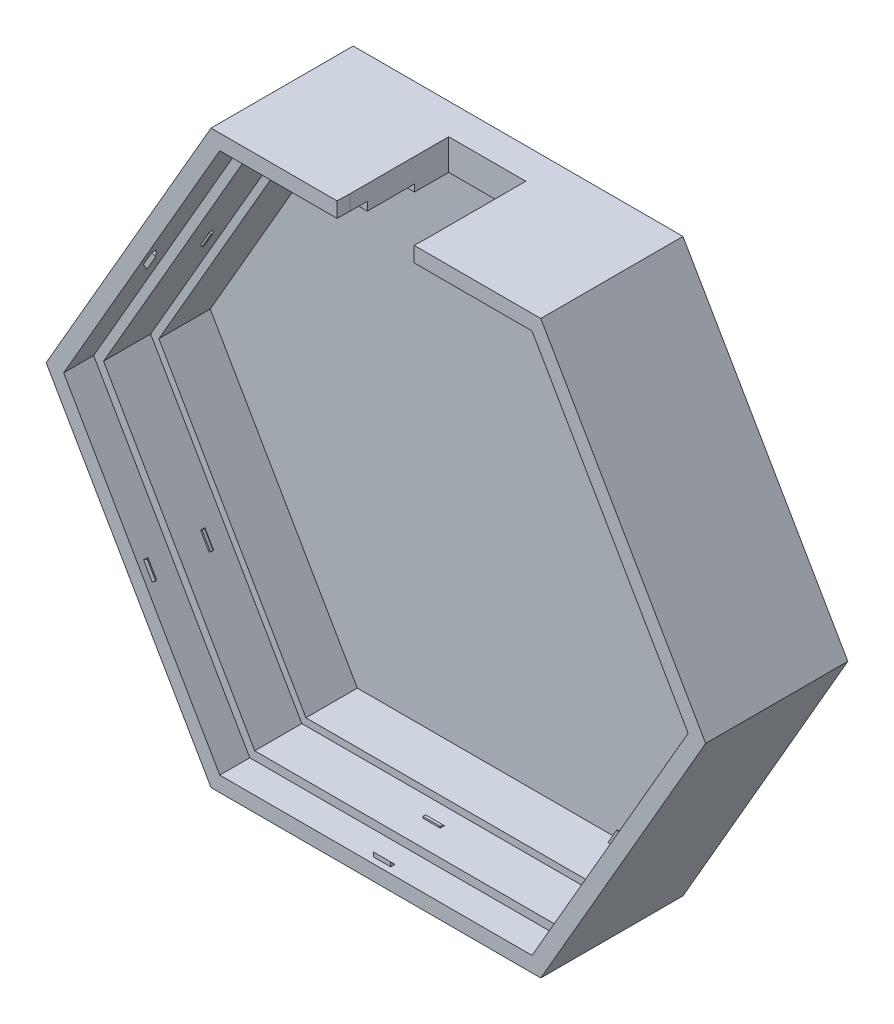
SolidWorks part; units mm, degrees
ref_plane "Front Plane" through (0, 0, 0) normal (0, 0, 1) x (1, 0, 0)
ref_plane "Top Plane" through (0, 0, 0) normal (0, 1, 0) x (1, 0, 0)
ref_plane "Right Plane" through (0, 0, 0) normal (1, 0, 0) x (0, 0, -1)
sketch "Sketch1" plane through (0, 0, 0) normal (0, 0, 1) x (1, 0, 0)
  line L1 (35.5, 0) -> (17.75, 30.7439)
  line L2 (17.75, 30.7439) -> (-17.75, 30.7439)
  line L3 (-17.75, 30.7439) -> (-35.5, 0)
  line L4 (-35.5, 0) -> (-17.75, -30.7439)
  line L5 (-17.75, -30.7439) -> (17.75, -30.7439)
  line L6 (17.75, -30.7439) -> (35.5, 0)
  line L7 (37.3475, 0) -> (18.6738, 32.3439)
  line L8 (18.6738, 32.3439) -> (-18.6738, 32.3439)
  line L9 (-18.6738, 32.3439) -> (-37.3475, 0)
  line L10 (-37.3475, 0) -> (-18.6738, -32.3439)
  line L11 (-18.6738, -32.3439) -> (18.6738, -32.3439)
  line L12 (18.6738, -32.3439) -> (37.3475, 0)
  circle A0 centre (0, 0) radius 30.7439 construction
  circle A1 centre (0, 0) radius 32.3439 construction
  dimension "D1" = 35.5
  dimension "D2" = 1.6
extrude "Boss-Extrude1" add sketch "Sketch1" along normal blind 10
sketch "Sketch2" plane through (0, 0, 0) normal (0, 0, -1) x (-1, 0, 0)
  line L1 (36.8475, 0) -> (18.4238, 31.9109)
  line L2 (18.4238, 31.9109) -> (-18.4238, 31.9109)
  line L3 (-18.4238, 31.9109) -> (-36.8475, 0)
  line L4 (-36.8475, 0) -> (-18.4238, -31.9109)
  line L5 (-18.4238, -31.9109) -> (18.4238, -31.9109)
  line L6 (18.4238, -31.9109) -> (36.8475, 0)
  circle A0 centre (0, 0) radius 31.9109 construction
extrude "Boss-Extrude2" add sketch "Sketch2" along normal blind 1.6
sketch "Sketch8" plane through (0, 0, 0) normal (0, 0, -1) x (-1, 0, 0)
  line L1 (18.6738, -32.3439) -> (37.3475, 0)
  line L2 (37.3475, 0) -> (18.6738, 32.3439)
  line L3 (18.6738, 32.3439) -> (-18.6738, 32.3439)
  line L4 (-18.6738, 32.3439) -> (-37.3475, 0)
  line L5 (-37.3475, 0) -> (-18.6738, -32.3439)
  line L6 (-18.6738, -32.3439) -> (18.6738, -32.3439)
  circle A0 centre (0, 0) radius 32.3439 construction
extrude "Boss-Extrude5" add sketch "Sketch8" along normal blind 1.6
sketch "Sketch9" plane through (0, 0, 0) normal (0, 0, 1) x (1, 0, 0)
  line L0 (-17.75, 30.7439) -> (-35.5, 0) construction
  line L1 (-34.3453, 0) -> (-17.1726, -29.7439)
  line L2 (-17.1726, -29.7439) -> (17.1726, -29.7439)
  line L3 (17.1726, -29.7439) -> (34.3453, 0)
  line L4 (34.3453, 0) -> (17.1726, 29.7439)
  line L5 (17.1726, 29.7439) -> (-17.1726, 29.7439)
  line L6 (-17.1726, 29.7439) -> (-34.3453, 0)
  line L8 (-17.75, 30.7439) -> (-35.5, 0)
  line L9 (-35.5, 0) -> (-17.75, -30.7439)
  line L10 (-17.75, -30.7439) -> (17.75, -30.7439)
  line L11 (17.75, -30.7439) -> (35.5, 0)
  line L12 (35.5, 0) -> (17.75, 30.7439)
  line L13 (17.75, 30.7439) -> (-17.75, 30.7439)
  circle A0 centre (0, 0) radius 29.7439 construction
  circle A1 centre (0, 0) radius 30.7439 construction
  dimension "D1" = 1
extrude "Boss-Extrude6" add sketch "Sketch9" along normal blind 2
sketch "Sketch10" plane through (0, 30.7439, 0) normal (0, -1, 0) x (1, 0, 0)
  line L0 (17.75, 2) -> (-17.75, 2) construction
  line L1 (-4.5, 2) -> (4.5, 2)
  line L2 (-4.5, 2) -> (-4.5, 10)
  line L3 (-4.5, 10) -> (4.5, 10)
  line L4 (4.5, 2) -> (4.5, 10)
  line L5 (17.75, 10) -> (-17.75, 10) construction
  line L6 (-17.75, 10) -> (-17.75, 2) construction
  dimension "D1" = 9
  dimension "D2" = 13.25
extrude "Cut-Extrude1" cut sketch "Sketch10" against normal blind 2
sketch "Sketch11" plane through (0, 0, 2) normal (0, 0, 1) x (1, 0, 0)
  line L1 (35.3, 0) -> (17.65, 30.5707)
  line L2 (17.65, 30.5707) -> (-17.65, 30.5707)
  line L3 (-17.65, 30.5707) -> (-35.3, 0)
  line L4 (-35.3, 0) -> (-17.65, -30.5707)
  line L5 (-17.65, -30.5707) -> (17.65, -30.5707)
  line L6 (17.65, -30.5707) -> (35.3, 0)
  line L7 (35.5, 0) -> (17.75, 30.7439)
  line L8 (17.75, 30.7439) -> (-17.75, 30.7439)
  line L9 (-17.75, 30.7439) -> (-35.5, 0)
  line L10 (-35.5, 0) -> (-17.75, -30.7439)
  line L11 (-17.75, -30.7439) -> (17.75, -30.7439)
  line L12 (17.75, -30.7439) -> (35.5, 0)
  circle A0 centre (0, 0) radius 30.5707 construction
  circle A1 centre (0, 0) radius 30.7439 construction
  dimension "D1" = 35.3
extrude "Boss-Extrude7" add sketch "Sketch11" along normal blind 8
sketch "Sketch12" plane through (0, 0, 10) normal (0, 0, 1) x (1, 0, 0)
  line L1 (37.3475, 0) -> (18.6738, 32.3439)
  line L2 (18.6738, 32.3439) -> (-18.6738, 32.3439)
  line L3 (-18.6738, 32.3439) -> (-37.3475, 0)
  line L4 (-37.3475, 0) -> (-18.6738, -32.3439)
  line L5 (-18.6738, -32.3439) -> (18.6738, -32.3439)
  line L6 (18.6738, -32.3439) -> (37.3475, 0)
  circle A0 centre (0, 0) radius 32.3439 construction
extrude "Cut-Extrude2" cut sketch "Sketch12" against normal blind 4
sketch "Sketch13" plane through (0, 30.7439, 0) normal (0, 1, 0) x (1, 0, 0)
  line L1 (4.5, -2) -> (-4.5, -2)
  line L2 (4.5, -2) -> (4.5, -6)
  line L3 (4.5, -6) -> (-4.5, -6)
  line L4 (-4.5, -2) -> (-4.5, -6)
extrude "Cut-Extrude3" cut sketch "Sketch13" against normal blind 4
sketch "Sketch16" plane through (0, 32.3439, 0) normal (0, 1, 0) x (1, 0, 0)
  line L0 (4.5, -2) -> (-4.5, -2)
  line L1 (-4.5, -2) -> (-4.5, 0)
  line L2 (-4.5, 0) -> (4.5, 0)
  line L3 (4.5, 0) -> (4.5, -2)
  dimension "D1" = 2
extrude "Cut-Extrude4" cut sketch "Sketch16" against normal blind 3
sketch "Sketch19" plane through (0, 0, -1.6) normal (0, 0, -1) x (-1, 0, 0)
  line L0 (-19.2511, 33.3439) -> (-38.5022, 0)
  line L1 (-18.6738, 32.3439) -> (-37.3475, 0)
  line L2 (-37.3475, 0) -> (-18.6738, -32.3439)
  line L3 (-18.6738, -32.3439) -> (18.6738, -32.3439)
  line L4 (18.6738, -32.3439) -> (37.3475, 0)
  line L5 (37.3475, 0) -> (18.6738, 32.3439)
  line L6 (18.6738, 32.3439) -> (-18.6738, 32.3439)
  line L7 (-38.5022, 0) -> (-19.2511, -33.3439)
  line L8 (-19.2511, -33.3439) -> (19.2511, -33.3439)
  line L9 (19.2511, -33.3439) -> (38.5022, 0)
  line L10 (38.5022, 0) -> (19.2511, 33.3439)
  line L11 (19.2511, 33.3439) -> (-19.2511, 33.3439)
  line L12 (-18.0964, -31.3439) -> (18.0964, -31.3439)
  line L13 (18.0964, -31.3439) -> (36.1928, 0)
  line L14 (36.1928, 0) -> (18.0964, 31.3439)
  line L15 (18.0964, 31.3439) -> (-18.0964, 31.3439)
  line L16 (-18.0964, 31.3439) -> (-36.1928, 0)
  line L17 (-36.1928, 0) -> (-18.0964, -31.3439)
  circle A0 centre (0, 0) radius 32.3439 construction
  line M13 (-18.6738, -32.3439) -> (18.6738, -32.3439)
  line M14 (18.6738, -32.3439) -> (37.3475, 0)
  line M15 (37.3475, 0) -> (18.6738, 32.3439)
  line M16 (18.6738, 32.3439) -> (-18.6738, 32.3439)
  line M17 (-18.6738, 32.3439) -> (-37.3475, 0)
  line M18 (-37.3475, 0) -> (-18.6738, -32.3439)
  dimension "D1" = 1
  dimension "D2" = 1
extrude "Boss-Extrude10" add sketch "Sketch19" against normal blind 7.6 contours L10 L11 L0 L7 L8 L9 M13 M18 M17 M16 M15 M14 region at (0, 33.242, -1.6)
sketch "Sketch21" plane through (0, 0, 6) normal (0, 0, 1) x (1, 0, 0)
  line L0 (4.5, 32.3439) -> (4.5, 33.3439)
  line L1 (-19.2511, 33.3439) -> (19.2511, 33.3439) construction
  line L2 (4.5, 33.3439) -> (-4.5, 33.3439)
  line L3 (-4.5, 33.3439) -> (-4.5, 32.3439)
  line L4 (-4.5, 32.3439) -> (4.5, 32.3439)
extrude "Cut-Extrude5" cut sketch "Sketch21" against normal blind 6
sketch "Sketch22" plane through (0, 0, 6) normal (0, 0, 1) x (1, 0, 0)
  line L0 (-35.3, 0) -> (-17.65, -30.5707) construction
  line L1 (-36.4547, 0) -> (-18.2274, -31.5707)
  line L2 (-18.2274, -31.5707) -> (18.2274, -31.5707)
  line L3 (18.2274, -31.5707) -> (36.4547, 0)
  line L4 (36.4547, 0) -> (18.2274, 31.5707)
  line L5 (18.2274, 31.5707) -> (-18.2274, 31.5707)
  line L6 (-18.2274, 31.5707) -> (-36.4547, 0)
  circle A0 centre (0, 0) radius 31.5707 construction
  dimension "D1" = 1
extrude "Cut-Extrude7" cut sketch "Sketch22" against normal blind 2.2
sketch "Sketch24" plane through (0, 0, -1.6) normal (0, 0, -1) x (-1, 0, 0)
  line L1 (-19.2511, -33.3439) -> (19.2511, -33.3439)
  line L2 (19.2511, -33.3439) -> (38.5022, 0)
  line L3 (38.5022, 0) -> (19.2511, 33.3439)
  line L4 (19.2511, 33.3439) -> (-19.2511, 33.3439)
  line L5 (-19.2511, 33.3439) -> (-38.5022, 0)
  line L6 (-38.5022, 0) -> (-19.2511, -33.3439)
  circle A0 centre (0, 0) radius 33.3439 construction
extrude "Boss-Extrude11" add sketch "Sketch24" along normal blind 2
sketch "Sketch25" plane through (0, 0, 0) normal (0, 0, 1) x (1, 0, 0)
  line L1 (-17.1726, 29.7439) -> (-34.3453, 0)
  line L2 (-34.3453, 0) -> (-17.1726, -29.7439)
  line L3 (-17.1726, -29.7439) -> (17.1726, -29.7439)
  line L4 (17.1726, -29.7439) -> (34.3453, 0)
  line L5 (34.3453, 0) -> (17.1726, 29.7439)
  line L6 (17.1726, 29.7439) -> (-17.1726, 29.7439)
  circle A0 centre (0, 0) radius 29.7439 construction
extrude "Cut-Extrude8" cut sketch "Sketch25" against normal blind 2
sketch "Sketch26" plane through (0, 0, 6) normal (0, 0, 1) x (1, 0, 0)
  line L1 (19.2511, 33.3439) -> (-19.2511, 33.3439)
  line L2 (-19.2511, 33.3439) -> (-38.5022, 0)
  line L3 (-38.5022, 0) -> (-19.2511, -33.3439)
  line L4 (-19.2511, -33.3439) -> (19.2511, -33.3439)
  line L5 (19.2511, -33.3439) -> (38.5022, 0)
  line L6 (38.5022, 0) -> (19.2511, 33.3439)
  line L7 (18.2274, 31.5707) -> (-18.2274, 31.5707)
  line L8 (-18.2274, 31.5707) -> (-36.4547, 0)
  line L9 (-36.4547, 0) -> (-18.2274, -31.5707)
  line L10 (-18.2274, -31.5707) -> (18.2274, -31.5707)
  line L11 (18.2274, -31.5707) -> (36.4547, 0)
  line L12 (36.4547, 0) -> (18.2274, 31.5707)
  circle A0 centre (0, 0) radius 33.3439 construction
  circle A1 centre (0, 0) radius 31.5707 construction
extrude "Boss-Extrude12" add sketch "Sketch26" along normal blind 2
sketch "Sketch27" plane through (0, 0, 3.8) normal (0, 0, 1) x (1, 0, 0)
  line L1 (-18.2274, 31.5707) -> (-36.4547, 0)
  line L2 (-36.4547, 0) -> (-18.2274, -31.5707)
  line L3 (-18.2274, -31.5707) -> (18.2274, -31.5707)
  line L4 (18.2274, -31.5707) -> (36.4547, 0)
  line L5 (36.4547, 0) -> (18.2274, 31.5707)
  line L6 (18.2274, 31.5707) -> (-18.2274, 31.5707)
  line L7 (-17.65, 30.5707) -> (-35.3, 0)
  line L8 (-35.3, 0) -> (-17.65, -30.5707)
  line L9 (-17.65, -30.5707) -> (17.65, -30.5707)
  line L10 (17.65, -30.5707) -> (35.3, 0)
  line L11 (35.3, 0) -> (17.65, 30.5707)
  line L12 (17.65, 30.5707) -> (-17.65, 30.5707)
  circle A0 centre (0, 0) radius 31.5707 construction
  circle A1 centre (0, 0) radius 30.5707 construction
extrude "Boss-Extrude13" add sketch "Sketch27" along normal blind 5.7
sketch "Sketch28" plane through (0, 0, 8) normal (0, 0, 1) x (1, 0, 0)
  line L1 (19.2511, 33.3439) -> (-19.2511, 33.3439)
  line L2 (-19.2511, 33.3439) -> (-38.5022, 0)
  line L3 (-38.5022, 0) -> (-19.2511, -33.3439)
  line L4 (-19.2511, -33.3439) -> (19.2511, -33.3439)
  line L5 (19.2511, -33.3439) -> (38.5022, 0)
  line L6 (38.5022, 0) -> (19.2511, 33.3439)
  line L7 (18.2274, 31.5707) -> (-18.2274, 31.5707)
  line L8 (-18.2274, 31.5707) -> (-36.4547, 0)
  line L9 (-36.4547, 0) -> (-18.2274, -31.5707)
  line L10 (-18.2274, -31.5707) -> (18.2274, -31.5707)
  line L11 (18.2274, -31.5707) -> (36.4547, 0)
  line L12 (36.4547, 0) -> (18.2274, 31.5707)
  circle A0 centre (0, 0) radius 33.3439 construction
  circle A1 centre (0, 0) radius 31.5707 construction
extrude "Boss-Extrude14" add sketch "Sketch28" along normal blind 5
sketch "Sketch29" plane through (0, 29.7439, 0) normal (0, -1, 0) x (-1, 0, 0)
  line L0 (4.5, 0) -> (4.5, 2)
  line L1 (-17.1726, 2) -> (17.1726, 2) construction
  line L2 (4.5, 2) -> (-4.5, 0)
  line L3 (-4.5, 0) -> (-4.5, 2)
  line L4 (-4.5, 2) -> (4.5, 2)
  line L5 (4.5, -1.7171) -> (4.5, -11.5038)
  line L6 (4.5, -2) -> (4.5, 0) construction
  line L7 (4.5, -11.5038) -> (-4.5, 0)
  line L8 (-4.5, -1.5451) -> (-4.5, -11.7394)
  line L9 (-4.5, 0) -> (-4.5, -2) construction
  line L10 (-4.5, -11.7394) -> (4.5, -11.5038)
  line L11 (4.5, -1.7171) -> (4.5, 0)
  line L12 (-4.5, -1.5451) -> (-4.5, 0)
  line M1 (4.5, 0) -> (4.5, -2)
  line M4 (17.1726, 2) -> (-17.1726, 2)
  line M7 (-4.5, -2) -> (-4.5, 0)
  line M8 (-4.5, 0) -> (4.5, 0)
extrude "Cut-Extrude9" cut sketch "Sketch29" against normal through all contours L8 L10 L7 M7 | L7 L5 M1 M8 | L0 L2 M8 | L3 L2 M4 region at (-1.5, 29.7439, -0.6667) region at (-1.5, 29.7439, 3.8346) region at (1.5, 29.7439, -1.3333) region at (1.5, 29.7439, 7.7477)
sketch "Sketch30" plane through (0, -30.5707, 0) normal (0, 1, 0) x (1, 0, 0)
  line L0 (-17.65, -9.5) -> (17.65, -9.5) construction
  line L1 (1, -9.5) -> (-1, -9.5)
  line L2 (1, -9.5) -> (1, -6)
  line L3 (1, -6) -> (-1, -6)
  line L4 (-1, -9.5) -> (-1, -6)
  line L5 (-17.65, -9.5) -> (-17.65, -2) construction
  line L6 (1, -6.5) -> (-1, -6.5)
  line L7 (-17.65, -2) -> (17.65, -2) construction
  dimension "D1" = 2
  dimension "D2" = 16.65
  dimension "D3" = 4
  dimension "D4" = 0.5
extrude "Boss-Extrude15" add sketch "Sketch30" along normal blind 0.2 contours L6 L2 L3 L4 region at (0, -30.5707, 6.25)
chamfer "Chamfer1" distance 0.2 angle 45 1 edges at (0, -30.3707, 6)
sketch "Sketch31" plane through (-26.475, -15.2853, 0) normal (0.866, 0.5, 0) x (0, 0, -1)
  line L0 (-2, 17.65) -> (-2, -17.65) construction
  line L1 (-6.5, -1) -> (-6, -1)
  line L2 (-6.5, -1) -> (-6.5, 1)
  line L3 (-6.5, 1) -> (-6, 1)
  line L4 (-6, -1) -> (-6, 1)
  line L5 (-9.5, -17.65) -> (-2, -17.65) construction
  dimension "D1" = 4
  dimension "D2" = 0.5
  dimension "D3" = 2
  dimension "D4" = 16.65
extrude "Boss-Extrude16" add sketch "Sketch31" along normal blind 0.2
chamfer "Chamfer2" distance 0.2 angle 45 1 edges at (-26.3018, -15.1853, 6)
sketch "Sketch32" plane through (-26.475, 15.2853, 0) normal (0.866, -0.5, 0) x (0, 0, -1)
  line L0 (-2, 17.65) -> (-2, -17.65) construction
  line L1 (-6.5, -1) -> (-6, -1)
  line L2 (-6.5, -1) -> (-6.5, 1)
  line L3 (-6.5, 1) -> (-6, 1)
  line L4 (-6, -1) -> (-6, 1)
  line L5 (-9.5, 17.65) -> (-2, 17.65) construction
  dimension "D1" = 0.5
  dimension "D2" = 2
  dimension "D3" = 4
  dimension "D4" = 16.65
extrude "Boss-Extrude17" add sketch "Sketch32" along normal blind 0.2
chamfer "Chamfer3" distance 0.2 angle 45 1 edges at (-26.3018, 15.1853, 6)
sketch "Sketch33" plane through (26.475, -15.2853, 0) normal (-0.866, 0.5, 0) x (0, 0, 1)
  line L0 (2, -17.65) -> (2, 17.65) construction
  line L1 (6.5, 1) -> (6, 1)
  line L2 (6.5, 1) -> (6.5, -1)
  line L3 (6.5, -1) -> (6, -1)
  line L4 (6, 1) -> (6, -1)
  line L5 (9.5, -17.65) -> (2, -17.65) construction
  dimension "D1" = 0.5
  dimension "D2" = 2
  dimension "D3" = 4
  dimension "D4" = 16.65
extrude "Boss-Extrude18" add sketch "Sketch33" along normal blind 0.2
chamfer "Chamfer4" distance 0.2 angle 45 1 edges at (26.3018, -15.1853, 6)
sketch "Sketch40" plane through (0, 0, 2) normal (0, 0, 1) x (1, 0, 0)
  line L1 (-17.65, 30.5707) -> (-35.3, 0)
  line L2 (-35.3, 0) -> (-17.65, -30.5707)
  line L3 (-17.65, -30.5707) -> (17.65, -30.5707)
  line L4 (17.65, -30.5707) -> (35.3, 0)
  line L5 (35.3, 0) -> (17.65, 30.5707)
  line L6 (17.65, 30.5707) -> (-17.65, 30.5707)
  line L7 (-17.1726, 29.7439) -> (-34.3453, 0)
  line L8 (-34.3453, 0) -> (-17.1726, -29.7439)
  line L9 (-17.1726, -29.7439) -> (17.1726, -29.7439)
  line L10 (17.1726, -29.7439) -> (34.3453, 0)
  line L11 (34.3453, 0) -> (17.1726, 29.7439)
  line L12 (17.1726, 29.7439) -> (-17.1726, 29.7439)
  circle A0 centre (0, 0) radius 30.5707 construction
  circle A1 centre (0, 0) radius 29.7439 construction
extrude "Boss-Extrude25" add sketch "Sketch40" along normal blind 2
sketch "Sketch34" plane through (26.475, 15.2853, 0) normal (-0.866, -0.5, 0) x (0, 0, 1)
  line L1 (6.5, 1) -> (6, 1)
  line L2 (6.5, 1) -> (6.5, -1)
  line L3 (6.5, -1) -> (6, -1)
  line L4 (6, 1) -> (6, -1)
  line L5 (9.5, -17.65) -> (4, -17.65) construction
  line L6 (4, -17.65) -> (4, 17.65) construction
  dimension "D1" = 0.5
  dimension "D2" = 2
  dimension "D3" = 2
  dimension "D4" = 16.65
extrude "Boss-Extrude19" add sketch "Sketch34" along normal blind 0.2
chamfer "Chamfer5" distance 0.2 angle 45 1 edges at (26.3018, 15.1853, 6)
sketch "Sketch41" plane through (0, 29.7439, 0) normal (0, -1, 0) x (-1, 0, 0)
  line L0 (4.5, 2) -> (4.5, -4)
  line L1 (-17.1726, -4) -> (17.1726, -4) construction
  line L2 (-4.5, 2) -> (-4.5, -4)
  line L3 (-4.5, -4) -> (4.5, -4)
  line L4 (4.5, 2) -> (-4.5, 2)
extrude "Cut-Extrude10" cut sketch "Sketch41" against normal blind 2
sketch "Sketch42" plane through (0, 29.7439, 0) normal (0, -1, 0) x (-1, 0, 0)
  line L1 (-17.1726, 2) -> (-4.5, 2) construction
  line L3 (-4.5, 2) -> (-4.5, -4) construction
  line L4 (4.5, 2) -> (17.1726, 2) construction
  line L5 (4.5, -4) -> (4.5, 2) construction
  circle A0 centre (-11, -1) radius 2.75
  circle A1 centre (11, -1) radius 2.75
  dimension "D1" = 5.5
  dimension "D4" = 5.5
  dimension "D2" = 3
  dimension "D3" = 6.5
  dimension "D5" = 3
  dimension "D6" = 6.5
extrude "Cut-Extrude11" cut sketch "Sketch42" against normal blind 3.2
sketch "Sketch44" plane through (0, -31.5707, 0) normal (0, 1, 0) x (1, 0, 0)
  line L0 (-18.2274, -13) -> (-18.2274, -9.5) construction
  line L5 (-18.2274, -9.5) -> (18.2274, -9.5) construction
  line L14 (1.0276, -12.3) -> (-0.9724, -12.3)
  line L15 (1.0276, -12.3) -> (1.0276, -11.8)
  line L16 (1.0276, -11.8) -> (-0.9724, -11.8)
  line L17 (-0.9724, -12.3) -> (-0.9724, -11.8)
  dimension "D1" = 2
  dimension "D2" = 0.5
  dimension "D3" = 17.255
  dimension "D4" = 2.3
sketch "Sketch45" plane through (27.341, -15.7853, 0) normal (-0.866, 0.5, 0) x (0, 0, 1)
  line L0 (13, -18.2274) -> (9.5, -18.2274) construction
  line L1 (12.3, 1.0276) -> (11.8, 1.0276)
  line L2 (12.3, 1.0276) -> (12.3, -0.9724)
  line L3 (12.3, -0.9724) -> (11.8, -0.9724)
  line L4 (11.8, 1.0276) -> (11.8, -0.9724)
  line L5 (9.5, -18.2274) -> (9.5, 18.2274) construction
  dimension "D1" = 2
  dimension "D2" = 0.5
  dimension "D3" = 17.255
  dimension "D4" = 2.3
sketch "Sketch47" plane through (27.341, 15.7853, 0) normal (-0.866, -0.5, 0) x (0, 0, 1)
  line L0 (13, -18.2274) -> (9.5, -18.2274) construction
  line L1 (12.3, 1.0276) -> (11.8, 1.0276)
  line L2 (12.3, 1.0276) -> (12.3, -0.9724)
  line L3 (12.3, -0.9724) -> (11.8, -0.9724)
  line L4 (11.8, 1.0276) -> (11.8, -0.9724)
  line L5 (9.5, -18.2274) -> (9.5, 18.2274) construction
  dimension "D1" = 0.5
  dimension "D2" = 2
  dimension "D3" = 17.255
  dimension "D4" = 2.3
sketch "Sketch49" plane through (-27.341, -15.7853, 0) normal (0.866, 0.5, 0) x (0, 0, -1)
  line L0 (-13, 18.2274) -> (-9.5, 18.2274) construction
  line L1 (-12.3, 0.9724) -> (-11.8, 0.9724)
  line L2 (-12.3, 0.9724) -> (-12.3, -1.0276)
  line L3 (-12.3, -1.0276) -> (-11.8, -1.0276)
  line L4 (-11.8, 0.9724) -> (-11.8, -1.0276)
  line L5 (-9.5, 18.2274) -> (-9.5, -18.2274) construction
  dimension "D1" = 0.5
  dimension "D2" = 2
  dimension "D3" = 17.255
  dimension "D4" = 2.3
sketch "Sketch50" plane through (-27.341, 15.7853, 0) normal (0.866, -0.5, 0) x (0, 0, -1)
  line L0 (-13, 18.2274) -> (-9.5, 18.2274) construction
  line L1 (-11.8, 0.9724) -> (-12.3, 0.9724)
  line L2 (-11.8, 0.9724) -> (-11.8, -1.0276)
  line L3 (-11.8, -1.0276) -> (-12.3, -1.0276)
  line L4 (-12.3, 0.9724) -> (-12.3, -1.0276)
  line L5 (-9.5, 18.2274) -> (-9.5, -18.2274) construction
  dimension "D1" = 2
  dimension "D2" = 0.5
  dimension "D3" = 17.255
  dimension "D4" = 2.3
extrude "Boss-Extrude27" add sketch "Sketch50" along normal blind 0.5
extrude "Boss-Extrude28" add sketch "Sketch49" along normal blind 0.5
extrude "Boss-Extrude29" add sketch "Sketch44" along normal blind 0.5
extrude "Boss-Extrude30" add sketch "Sketch45" along normal blind 0.5
extrude "Boss-Extrude31" add sketch "Sketch47" along normal blind 0.5
chamfer "Chamfer6" distance 0.5 angle 45 1 edges at (26.8942, 15.5593, 11.8)
chamfer "Chamfer7" distance 0.5 angle 45 1 edges at (26.9218, -15.5114, 11.8)
chamfer "Chamfer8" distance 0.5 angle 45 1 edges at (0.0276, -31.0707, 11.8)
chamfer "Chamfer9" distance 0.5 angle 45 1 edges at (-26.8942, -15.5593, 11.8)
chamfer "Chamfer10" distance 0.5 angle 45 1 edges at (-26.9218, 15.5114, 11.8)
sketch "Sketch52" plane through (0, 33.3439, 0) normal (0, 1, 0) x (1, 0, 0)
  line L0 (4.5, -11.7394) -> (-4.5, -11.5038)
  line L1 (-4.5, -11.5038) -> (-4.5392, -13)
  line L2 (19.2511, -13) -> (-19.2511, -13) construction
  line L3 (-4.5392, -13) -> (4.467, -13)
  line L4 (4.467, -13) -> (4.5, -11.7394)
extrude "Cut-Extrude12" cut sketch "Sketch52" against normal blind 30
sketch "Sketch53" plane through (0, 33.3439, 0) normal (0, 1, 0) x (1, 0, 0)
  line L0 (4.5, 2) -> (-4.5, 2)
  line L1 (-4.5, 2) -> (-4.5, 0)
  line L2 (-4.5, 2) -> (-4.5, -11.5038) construction
  line L3 (-4.5, 0) -> (4.5, 0)
  line L4 (4.5, 2) -> (4.5, -11.7394) construction
  line L5 (4.5, 0) -> (4.5, 2)
extrude "Boss-Extrude32" add sketch "Sketch53" against normal blind 3.6
